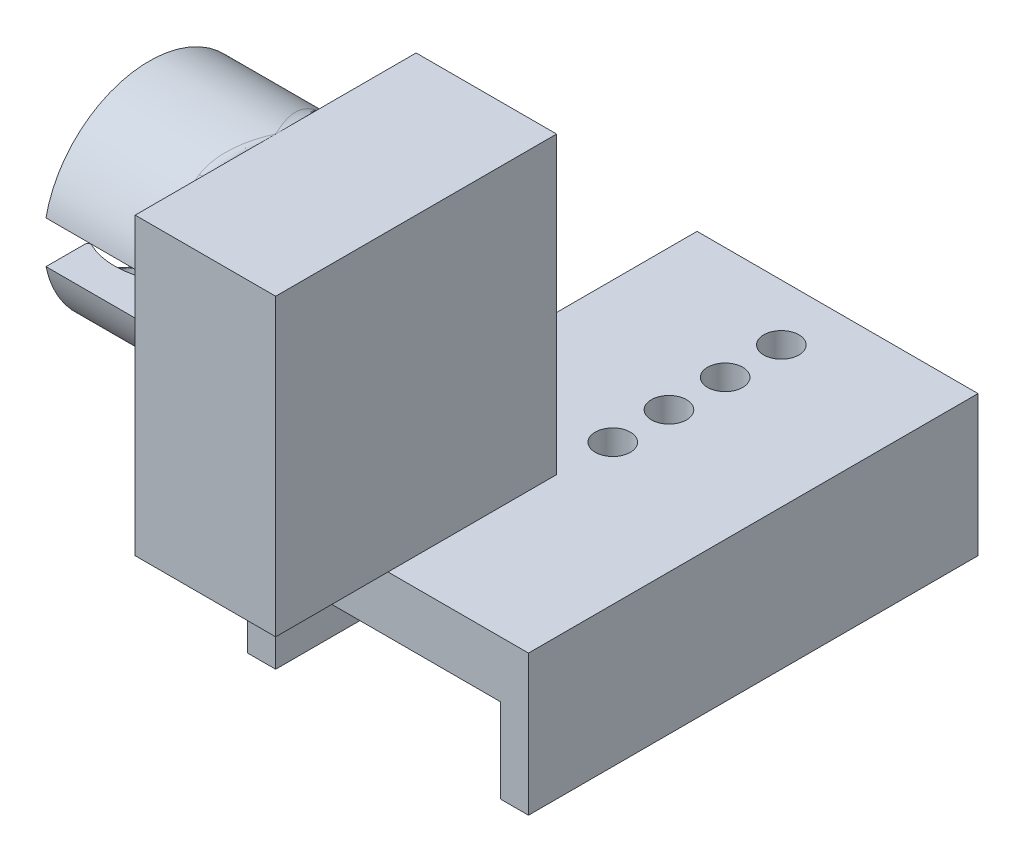
SolidWorks part; units mm, degrees
ref_plane "Front Plane" through (0, 0, 0) normal (0, 0, 1) x (1, 0, 0)
ref_plane "Top Plane" through (0, 0, 0) normal (0, 1, 0) x (1, 0, 0)
ref_plane "Right Plane" through (0, 0, 0) normal (1, 0, 0) x (0, 0, -1)
sketch "Sketch1" plane through (0, 0, 0) normal (0, 1, 0) x (1, 0, 0)
  line L1 (-5, 8) -> (5, 8)
  line L2 (-5, 8) -> (-5, -8)
  line L3 (-5, -8) -> (5, -8)
  line L4 (5, 8) -> (5, -8)
  line L5 (-5, 8) -> (5, -8) construction
  line L6 (-5, -8) -> (5, 8) construction
  point P0 (0, 0)
  dimension "D1" = 10
  dimension "D2" = 16
extrude "Base Extrude" add sketch "Sketch1" along normal blind 2
sketch "Sketch2" plane through (0, 0, 0) normal (0, -1, 0) x (1, 0, 0)
  line L0 (-5, 8) -> (5, 8) construction
  line L1 (5, -8) -> (4, -8)
  line L2 (5, -8) -> (5, 8)
  line L3 (5, 8) -> (4, 8)
  line L4 (4, -8) -> (4, 8)
  line L6 (-5, -8) -> (-4, -8)
  line L7 (-5, -8) -> (-5, 8)
  line L8 (-5, 8) -> (-4, 8)
  line L9 (-4, -8) -> (-4, 8)
  dimension "D1" = 1
  dimension "D2" = 1
extrude "Side Rails" add sketch "Sketch2" along normal blind 3
sketch "Sketch3" plane through (0, 2, 0) normal (0, 1, 0) x (1, 0, 0)
  line L5 (-5, 8) -> (-5, -8) construction
  line L6 (-5, -2) -> (0, -2)
  line L7 (-5, -2) -> (-5, -12)
  line L8 (-5, -12) -> (0, -12)
  line L9 (0, -2) -> (0, -12)
  dimension "D1" = 5
  dimension "D2" = 10
  dimension "D3" = 6
extrude "Ball Joint Post" add sketch "Sketch3" along normal blind 10.5
sketch "Sketch4" plane through (-5, 0, 0) normal (-1, 0, 0) x (0, 0, 1)
  line L0 (7, 12.5) -> (7, 8.75) construction
  line L1 (2, 12.5) -> (12, 12.5) construction
  circle A0 centre (7, 8.75) radius 3.75
  dimension "D1" = 3.75
extrude "Boss-Extrude1" add sketch "Sketch4" along normal blind 4.5
ref_plane "Plane1" through (-8.3, 0, 0) normal (-1, 0, 0) x (0, 0, 1)
sketch "Sketch6" plane through (-8.3, 0, 0) normal (-1, 0, 0) x (0, 0, 1)
  line L0 (7, 6.2) -> (7, 11.3)
  circle A0 centre (7, 8.75) radius 2.55
  dimension "D1" = 5.1
revolve "Cut-Revolve2" cut sketch "Sketch6" angle 360 about L0 region at (-8.3, 8.75, 5.9177) reverse direction yes
sketch "Sketch7" plane through (-5, 0, 0) normal (-1, 0, 0) x (0, 0, 1)
  line L0 (7, 12.5) -> (7, 8.75) construction
  line L1 (2, 12.5) -> (2, 2) construction
  line L2 (12, 8) -> (2, 8)
  line L3 (12, 8) -> (12, 9.5)
  line L4 (12, 9.5) -> (2, 9.5)
  line L5 (2, 8) -> (2, 9.5)
  line L6 (12, 8) -> (2, 9.5) construction
  line L7 (12, 9.5) -> (2, 8) construction
  dimension "D1" = 3.75
  dimension "D2" = 1.5
extrude "Cut-Extrude2" cut sketch "Sketch7" along normal up to surface (4.5 mm away) up to face at (-9.5, 8.75, 9.25)
fillet "Fillet1" radius 0.1 2 edges at (-9.5, 11, 7) (-9.5, 6.5, 7)
fillet "Fillet2" radius 0.7 5 edges at (-5, 11.6547, 4.6283) (-5, 9.5, 7) (-5, 8, 7) (-5, 11.6547, 9.3717) (-5, 5, 7)
sketch "Sketch8" plane through (0, 2, 0) normal (0, 1, 0) x (1, 0, 0)
  circle A0 centre (0, 6) radius 0.625
  circle A1 centre (0, 4) radius 0.625
  circle A2 centre (0, 2) radius 0.625
  circle A3 centre (0, 0) radius 0.625
  dimension "D3" = 1.25
  dimension "D1" = 2
  dimension "D2" = 5
  dimension "D5" = 2
  dimension "D4" = 4
extrude "Cut-Extrude3" cut sketch "Sketch8" against normal up to surface (2 mm away) up to face at (0, 0, 0)
